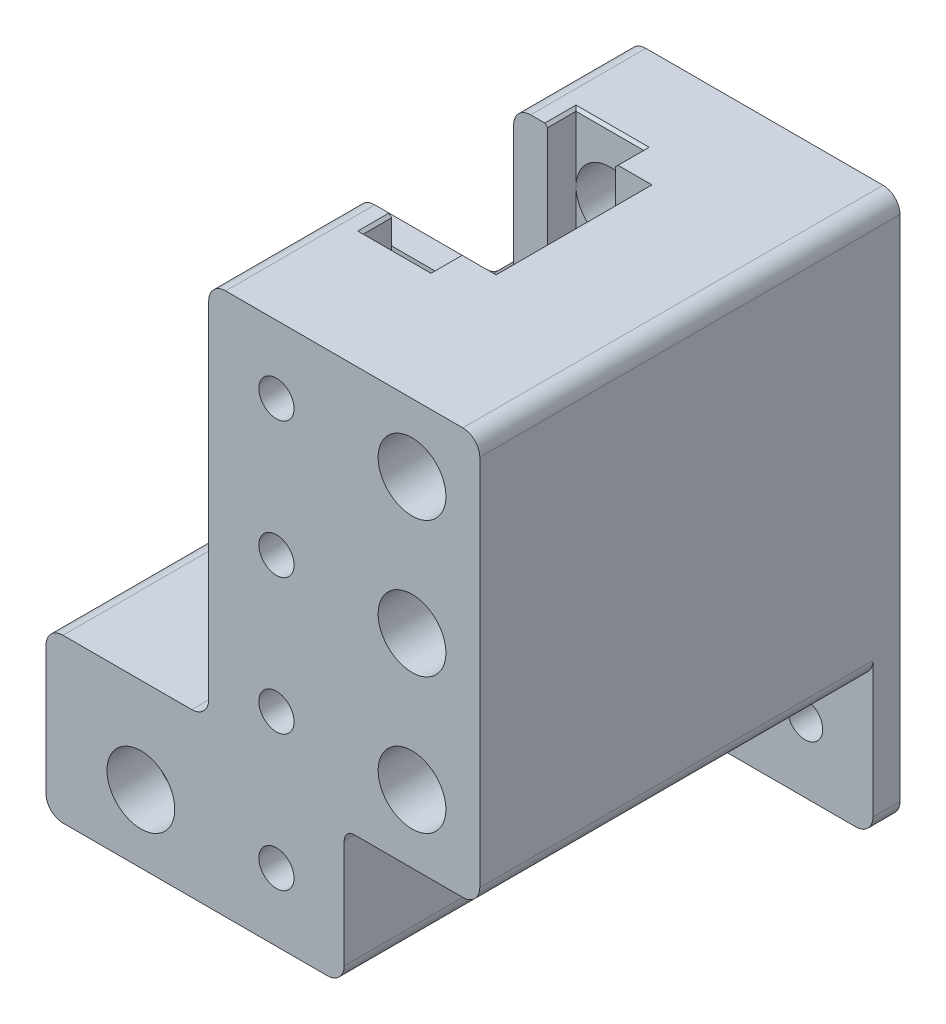
SolidWorks part; units mm, degrees
ref_plane "Спереди" through (0, 0, 0) normal (0, 0, 1) x (1, 0, 0)
ref_plane "Сверху" through (0, 0, 0) normal (0, 1, 0) x (1, 0, 0)
ref_plane "Справа" through (0, 0, 0) normal (1, 0, 0) x (0, 0, -1)
sketch "Эскиз1" plane through (0, 0, 0) normal (0, 0, 1) x (1, 0, 0)
  line L0 (0, 0) -> (80, 0)
  line L1 (80, 0) -> (80, 40)
  line L3 (40, 80) -> (0, 80)
  line L4 (0, 80) -> (0, 0)
  line L5 (80, 40) -> (60, 40)
  line L6 (60, 40) -> (40, 60)
  line L7 (40, 60) -> (40, 80)
  dimension "D1" = 80
  dimension "D2" = 80
  dimension "D3" = 40
  dimension "D4" = 40
  dimension "D5" = 40
  dimension "D6" = 40
  dimension "D7" = 20
  dimension "D8" = 20
extrude "Бобышка-Вытянуть1" add sketch "Эскиз1" along normal blind 4
sketch "Эскиз7" plane through (0, 0, 4) normal (0, 0, 1) x (1, 0, 0)
  line L7 (80, 0) -> (80, 40) construction
  line L10 (64, 24) -> (64, 0)
  line L11 (0, 20) -> (20, 20)
  line L12 (20, 20) -> (20, 0)
  line L13 (64, 24) -> (40, 24)
  line L17 (0, 80) -> (0, 0)
  line L18 (0, 0) -> (80, 0)
  line L19 (80, 0) -> (80, 40)
  line L20 (80, 40) -> (60, 40)
  line L21 (60, 40) -> (40, 60)
  line L22 (40, 60) -> (40, 80)
  line L23 (40, 80) -> (0, 80)
  line L24 (0, 80) -> (0, 20)
  line L25 (20, 0) -> (64, 0)
  line L29 (40, 24) -> (40, 80)
  line L30 (40, 80) -> (0, 80)
  dimension "D1" = 0
  dimension "D2" = 20
  dimension "D3" = 20
  dimension "D4" = 24
  dimension "D5" = 16
extrude "Бобышка-Вытянуть3" add sketch "Эскиз7" along normal blind 58
ref_plane "Плоскость1" through (0, 0, 28.5) normal (0, 0, 1) x (1, 0, 0)
ref_plane "Плоскость2" through (0, 0, 42.5) normal (0, 0, 1) x (1, 0, 0)
sketch "Эскиз9" plane through (0, 0, 28.5) normal (0, 0, 1) x (1, 0, 0)
  line L0 (40, 80) -> (0, 80) construction
  line L1 (20, 80) -> (40, 80)
  line L2 (20, 80) -> (20, 24)
  line L3 (21.2, 4) -> (38.8, 4)
  line L4 (40, 80) -> (40, 24)
  line L6 (20, 0) -> (64, 0) construction
  line L7 (40, 24) -> (38.8, 24)
  line L8 (38.8, 24) -> (38.8, 4)
  line L9 (20, 24) -> (21.2, 24)
  line L10 (21.2, 24) -> (21.2, 4)
  dimension "D1" = 4
  dimension "D2" = 1.2
  dimension "D3" = 20
  dimension "D4" = 20
extrude "Вырез-Вытянуть6" cut sketch "Эскиз9" along normal mid plane 23
sketch "Эскиз8" plane through (0, 0, 28.5) normal (0, 0, 1) x (1, 0, 0)
  line L0 (25, 10) -> (25, 80)
  line L1 (35, 80) -> (35, 10)
  line L5 (20, 0) -> (64, 0) construction
  line L10 (25, 80) -> (35, 80)
  line L11 (40, 80) -> (0, 80) construction
  line L12 (80, 0) -> (80, 40) construction
  arc A1 (25, 10) -> (35, 10) centre (30, 10) ccw
  dimension "D1" = 50
  dimension "D2" = 10
  dimension "D4" = 10
extrude "Вырез-Вытянуть4" cut sketch "Эскиз8" against normal mid plane 31.4
sketch "Эскиз6" plane through (0, 0, 42.5) normal (0, 0, 1) x (1, 0, 0)
  line L0 (41.6, 24) -> (45, 24)
  line L1 (45, 24) -> (45, 18.6603)
  line L3 (80, 0) -> (80, 40) construction
  line L6 (64, 0) -> (80, 0) construction
  line L11 (41.6, 24) -> (41.6, 15.4259)
  line L13 (60, 10) -> (60, 5.6)
  line L16 (64, 0) -> (40, 0)
  line L17 (40, 0) -> (40, 10)
  line L18 (64, 24) -> (40, 24) construction
  line L19 (64, 0) -> (64, 24) construction
  line L21 (64, 0) -> (64, 5.6)
  line L22 (64, 5.6) -> (60, 5.6)
  arc A1 (60, 10) -> (45, 18.6603) centre (50, 10) ccw
  arc A2 (41.6, 15.4259) -> (40, 10) centre (50, 10) ccw
  dimension "D1" = 20
  dimension "D5" = 3.4
  dimension "D6" = 4
  dimension "D3" = 10
  dimension "D4" = 8.4
  dimension "D2" = 30
  dimension "D7" = 4.4
extrude "Вырез-Вытянуть3" cut sketch "Эскиз6" along normal mid plane 15
sketch "Эскиз11" plane through (0, 0, 0) normal (0, 0, -1) x (-1, 0, 0)
  line L0 (0, 80) -> (0, 0) construction
  line L1 (0, 0) -> (-80, 0) construction
  line L2 (-10, 10) -> (-30, 10) construction
  line L3 (-10, 10) -> (-10, 30) construction
  line L4 (-30, 10) -> (-50, 10) construction
  circle A0 centre (-10, 10) radius 2.6
  circle A2 centre (-30, 30) radius 2.6
  circle A3 centre (-30, 50) radius 2.6
  circle A4 centre (-30, 70) radius 2.6
  circle A5 centre (-10, 30) radius 2.6
  circle A6 centre (-10, 50) radius 2.6
  circle A7 centre (-10, 70) radius 2.6
  circle A8 centre (-50, 10) radius 2.6
  circle A9 centre (-50, 30) radius 2.6
  circle A10 centre (-70, 10) radius 2.6
  circle A11 centre (-70, 30) radius 2.6
  circle A12 centre (-30, 10) radius 2.6 [skipped]
  circle A13 centre (-30, 10) radius 2.6
  dimension "D1" = 5.2
  dimension "D2" = 10
  dimension "D3" = 10
  dimension "D6" = 90
  dimension "D7" = 20
  dimension "D8" = 20
  dimension "D10" = 20
  dimension "D4" = 2
  dimension "D5" = 4
  dimension "D9" = 3
extrude "Вырез-Вытянуть7" cut sketch "Эскиз11" against normal through all and the other way through all
sketch "Эскиз12" plane through (0, 0, 62) normal (0, 0, 1) x (1, 0, 0)
  circle A0 centre (10, 70) radius 5
  circle A3 centre (10, 50) radius 5
  circle A4 centre (10, 30) radius 5
  dimension "D1" = 10
extrude "Вырез-Вытянуть8" cut sketch "Эскиз12" against normal up to surface (58 mm away) up to face at (72.6, 30, 4)
sketch "Эскиз16" plane through (0, 0, 17) normal (0, 0, 1) x (1, 0, 0)
  circle A0 centre (30, 70) radius 5
  circle A1 centre (30, 50) radius 5
  circle A2 centre (30, 30) radius 5
  circle A3 centre (30, 10) radius 5
  dimension "D1" = 10
extrude "Вырез-Вытянуть11" cut sketch "Эскиз16" against normal up to surface (13 mm away) up to face at (72.6, 30, 4)
sketch "Эскиз13" plane through (0, 0, 62) normal (0, 0, 1) x (1, 0, 0)
  circle A0 centre (50, 10) radius 5
extrude "Вырез-Вытянуть9" cut sketch "Эскиз13" against normal offset from surface (7 mm away) 5 up to face at (52.6, 10, 50)
sketch "Эскиз14" plane through (0, 0, 0) normal (0, -1, 0) x (1, 0, 0)
  line L0 (58.5441, 28.5) -> (-58.5441, 28.5) construction
  line L1 (20, 62) -> (20, 4) construction
  circle A0 centre (30, 28.5) radius 2.6
  dimension "D1" = 10
  dimension "D2" = 5.2
extrude "Вырез-Вытянуть10" cut sketch "Эскиз14" against normal up to surface (4 mm away) up to face at (30, 4, 28.5)
chamfer "Фаска1" distance 0.4 angle 45 9 edges at (21.2, 24, 28.5) (38.8, 24, 28.5) (35, 80, 14.9) (35, 80, 42.1) (30, 80, 44.2) (25, 80, 42.1) (20, 80, 28.5) (25, 80, 14.9) (30, 80, 12.8)
fillet "Скругление1" radius 1.5 1 edges at (20, 20, 33)
fillet "Скругление2" radius 2.5 15 edges at (0, 80, 31) (40, 80, 8.5) (40, 60, 2) (60, 40, 2) (80, 40, 2) (80, 0, 2) (0, 0, 2) (64, 0, 56) (64, 0, 19.5) (64, 24, 33) (20, 0, 33) (0, 20, 33) (40, 24, 10.5) (40, 24, 51) (40, 80, 51)
mirror "Зеркальное отражение1" about plane through (0, 0, 0) normal (1, 0, 0) of bodies 115
delete or keep bodies "Тело-Удалить/Сохранить 1" type delete bodies bodies 115
